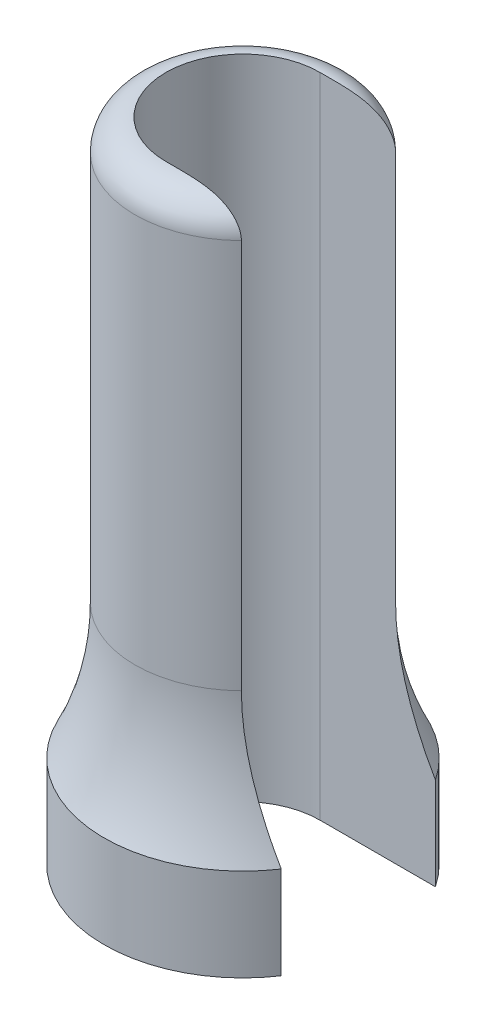
SolidWorks part; units mm, degrees
ref_plane "Front Plane" through (0, 0, 0) normal (0, 0, 1) x (1, 0, 0)
ref_plane "Top Plane" through (0, 0, 0) normal (0, 1, 0) x (1, 0, 0)
ref_plane "Right Plane" through (0, 0, 0) normal (1, 0, 0) x (0, 0, -1)
sketch "Sketch1" plane through (0, 0, 0) normal (0, 1, 0) x (1, 0, 0)
  circle A1 centre (0, 0) radius 4.5
extrude "Boss-Extrude1" add sketch "Sketch1" along normal blind 3
sketch "Sketch2" plane through (0, 3, 0) normal (0, 1, 0) x (1, 0, 0)
  circle A0 centre (0, 0) radius 3.5
extrude "Boss-Extrude2" add sketch "Sketch2" along normal blind 18
sketch "Sketch3" plane through (0, 21, 0) normal (0, 1, 0) x (1, 0, 0)
  line L0 (0, 2.5) -> (2.4495, 2.5)
  line L1 (0, -2.5) -> (2.4495, -2.5)
  arc A0 (0, 2.5) -> (0, -2.5) centre (0, 0) ccw
  circle A1 centre (0, 0) radius 3.5 construction
  arc A2 (2.4495, -2.5) -> (2.4495, 2.5) centre (0, 0) ccw
extrude "Cut-Extrude2" cut sketch "Sketch3" against normal blind 22.5
sketch "Sketch4" plane through (0, 3, 0) normal (0, 1, 0) x (1, 0, 0)
  line L0 (2.4495, -2.5) -> (3.7417, -2.5)
  line L1 (2.4495, 2.5) -> (3.7417, 2.5)
  circle A0 centre (0, 0) radius 4.5 construction
  arc A1 (2.4495, -2.5) -> (2.4495, 2.5) centre (0, 0) ccw
  arc A2 (3.7417, -2.5) -> (3.7417, 2.5) centre (0, 0) ccw
extrude "Cut-Extrude3" cut sketch "Sketch4" against normal blind 19.5
fillet "Fillet1" radius 10 1 edges at (-3.5, 3, 0)
fillet "Fillet2" radius 1 1 edges at (-3.5, 21, 0)
